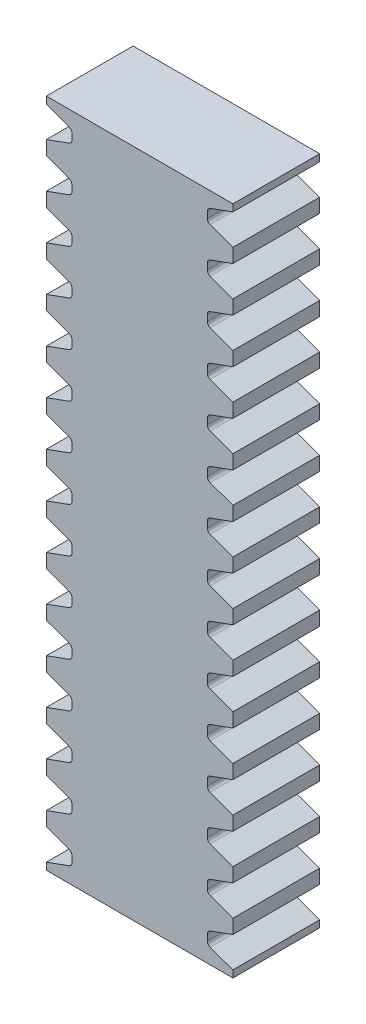
SolidWorks part; units mm, degrees
ref_plane "Front Plane" through (0, 0, 0) normal (0, 0, 1) x (1, 0, 0)
ref_plane "Top Plane" through (0, 0, 0) normal (0, 1, 0) x (1, 0, 0)
ref_plane "Right Plane" through (0, 0, 0) normal (1, 0, 0) x (0, 0, -1)
ref_axis "Axis1" through (0, -55, 0) along (0, 1, 0)
sketch "SketchCI.m_strSketchName" plane through (0, 0, 0) normal (0, 0, 1) x (1, 0, 0)
  line L0 (-1.0494, 2.0606) -> (-1.0494, -59.7565)
  line L1 (-1.0494, -59.7565) -> (7.551, -59.7565)
  line L2 (7.551, -59.7565) -> (7.551, 2.0606)
  line L3 (7.551, 2.0606) -> (-1.0494, 2.0606)
  dimension "D1" = 1.0494
  dimension "D2" = 59.7565
  dimension "D3" = 7.551
  dimension "D4" = 2.0606
extrude "ExtrudeCI" add sketch "SketchCI.m_strSketchName" along normal blind 4 and the other way blind 4
sketch "SketchToothGeartrax1Gear" plane through (0, 0, 0) normal (0, 0, 1) x (1, 0, 0)
  line L0 (-1.0494, 1.4123) -> (-1.0494, -1.4123)
  line L1 (-1.0494, -1.4123) -> (1.0529, -0.6471)
  line L2 (1.3118, -0.2773) -> (1.3118, 0.2773)
  line L3 (1.0529, 0.6471) -> (-1.0494, 1.4123)
  arc A0 (1.0529, -0.6471) -> (1.3118, -0.2773) centre (0.9183, -0.2773) ccw
  arc A1 (1.3118, 0.2773) -> (1.0529, 0.6471) centre (0.9183, 0.2773) ccw
  dimension "D1" = 0.7871
  dimension "D2" = 0.7871
  dimension "ADDENDUM" = 1.0494
  dimension "FLANKONE" = 0.9682
  dimension "FLANKONEANGLE" = 70
  dimension "DEDENDUM" = 1.3118
  dimension "FLANKTWO" = 0.9682
  dimension "FLANKTWOANGLE" = 70
extrude "ToothExtrudeCutGeartrax1Gear" cut sketch "SketchToothGeartrax1Gear" against normal blind 4 and the other way blind 4
pattern_linear "PatternGeartrax1Gear" count 15 spacing 4.1211 along (0, -1, 0) of "ToothExtrudeCutGeartrax1Gear"
sketch "AuxiliarySketchGeartrax1Gear" plane through (0, 0, 0) normal (0, 0, 1) x (1, 0, 0)
  line L0 (0, 0) -> (0, -61.8171) construction
mirror "Mirror1" about plane through (7.551, -59.7565, -4) normal (1, 0, 0) of "ExtrudeCI", "ToothExtrudeCutGeartrax1Gear", "PatternGeartrax1Gear"
